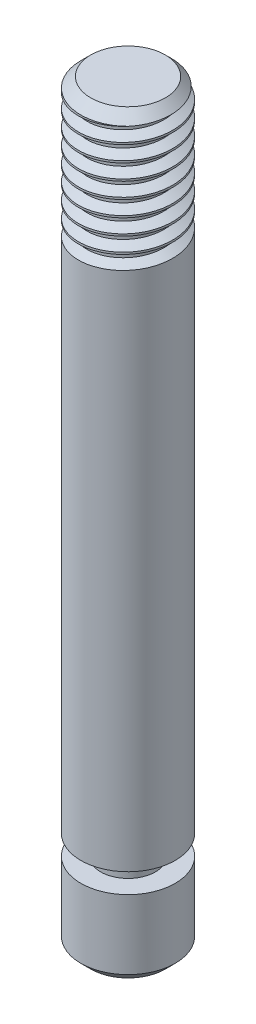
SolidWorks part; units mm, degrees
ref_plane "Front Plane" through (0, 0, 0) normal (0, 0, 1) x (1, 0, 0)
ref_plane "Top Plane" through (0, 0, 0) normal (0, 1, 0) x (1, 0, 0)
ref_plane "Right Plane" through (0, 0, 0) normal (1, 0, 0) x (0, 0, -1)
sketch "Sketch1" plane through (0, 0, 0) normal (0, 1, 0) x (1, 0, 0)
  circle A0 centre (0, 0) radius 2.3813
  dimension "D1" = 4.7625
extrude "Boss-Extrude1" add sketch "Sketch1" along normal blind 38.1
chamfer "Chamfer1" distance 0.5 angle 45 2 edges at (0, 0, 2.3813) (0, 38.1, 2.3813)
thread "Thread1" pitch 0.8 method cut trim with start face yes trim with end face yes profile "Thread Profile1" start angle 0, offset 0, length 6.35, pitch 0.8, diameter 4.7625
ref_plane "Plane1" through (-2.3813, 38.1, 0) normal (0, 0, 1) x (-1, 0, 0)
sketch "Thread Profile1" plane through (-2.3813, 38.1, 0) normal (0, 0, 1) x (-1, 0, 0)
  line L0 (0, 0) -> (0, 0.8) construction
  line L11 (0, 0) -> (0, 0.7)
  line L12 (0, 0.7) -> (-0.433, 0.45)
  line L13 (-0.433, 0.45) -> (-0.433, 0.25)
  line L15 (-0.433, 0.25) -> (0, 0)
  line L17 (-0.433, 0.35) -> (0, 0.35) construction
  point P2 (0, 0)
  dimension "Pitch" = 0.8
  dimension "Profile_Angle" = 60
  dimension "Profile_Land" = 0.2
  dimension "Profile_Height" = 0.433
sketch "Sketch17" plane through (0, 0, 0) normal (0, 0, 1) x (1, 0, 0)
  line L0 (-2.3813, 4) -> (-1.3813, 4)
  line L1 (-2.3813, 31.8) -> (-2.3813, 0.5) construction
  line L2 (-1.3813, 4) -> (-1.3813, 5)
  line L3 (-1.3813, 5) -> (-2.3813, 5)
  line L4 (-2.3813, 4) -> (-2.3813, 5)
  line L5 (0, 0) -> (0, 55.4424) construction
  line L6 (-1.8812, 0) -> (1.8812, 0) construction
  dimension "D1" = 1
  dimension "D2" = 1
  dimension "D3" = 4
revolve "Cut-Revolve1" cut sketch "Sketch17" angle 360 about L5
